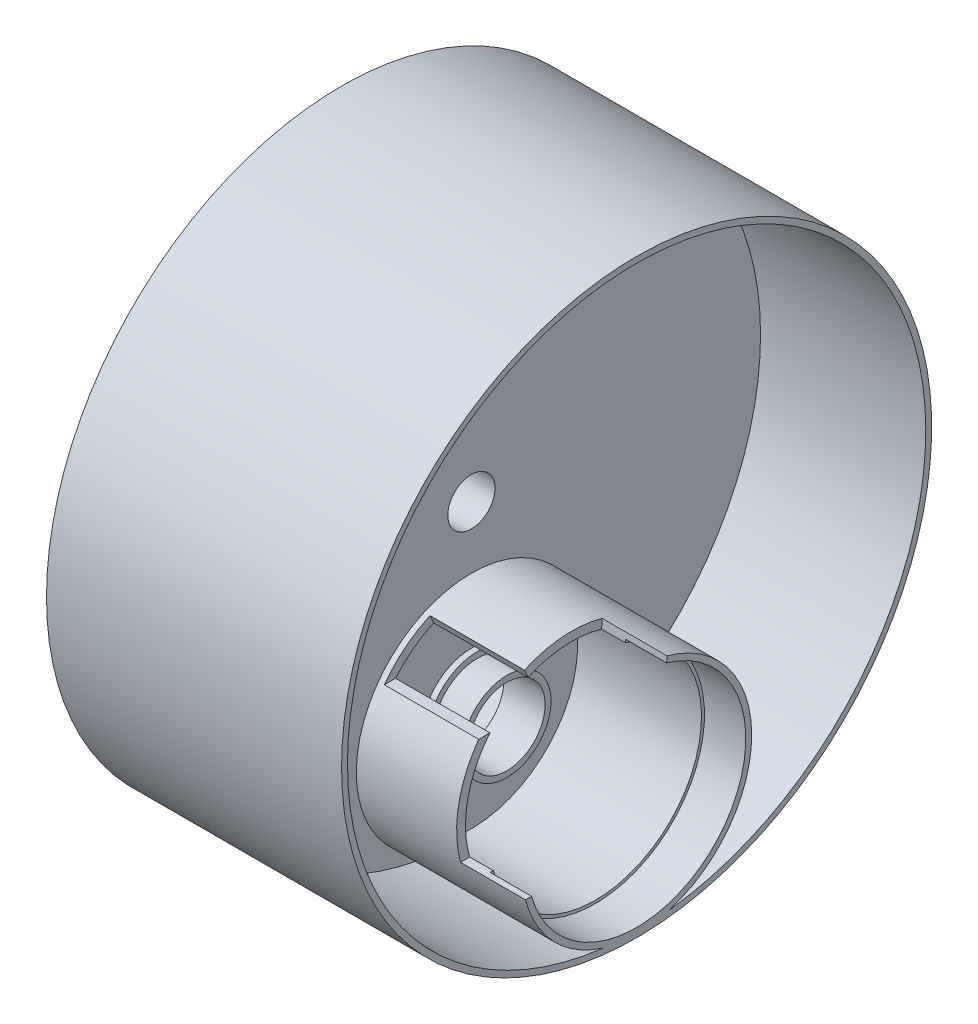
SolidWorks part; units mm, degrees
material "1060 Сплав"
ref_plane "Спереди" through (0, 0, 0) normal (0, 0, 1) x (1, 0, 0)
ref_plane "Сверху" through (0, 0, 0) normal (0, 1, 0) x (1, 0, 0)
ref_plane "Справа" through (0, 0, 0) normal (1, 0, 0) x (0, 0, -1)
sketch "Эскиз1" plane through (0, 0, 0) normal (0, 0, 1) x (1, 0, 0)
  line L0 (0, 0) -> (26039.5549, 0) construction
  line L1 (-27, 7.5) -> (-27, 8.5)
  line L2 (0, 19.5) -> (-29, 19.5)
  line L3 (-29, 19.5) -> (-29, 6.5)
  line L4 (-29, 6.5) -> (-22, 6.5)
  line L5 (-22, 6.5) -> (-22, 7.5)
  line L6 (-22, 7.5) -> (-27, 7.5)
  line L7 (-28, 8.5) -> (-28, 18)
  line L8 (-28, 18) -> (-7, 18)
  line L9 (-7, 18) -> (-7, 18.5)
  line L10 (-7, 18.5) -> (0, 18.5)
  line L11 (0, 18.5) -> (0, 19.5)
  line L12 (-27, 8.5) -> (-28, 8.5)
  dimension "D1" = 18.5
  dimension "D2" = 1
  dimension "D3" = 18
  dimension "D4" = 7
  dimension "D5" = 21
  dimension "D6" = 1
  dimension "D7" = 1
  dimension "D8" = 1
  dimension "D9" = 7.5
  dimension "D10" = 1
  dimension "D11" = 13
  dimension "D12" = 0.5
  dimension "D13" = 5
revolve "Повернуть1" add sketch "Эскиз1" angle 360 about L0
sketch "Эскиз2" plane through (0, 0, 0) normal (1, 0, 0) x (0, 0, -1)
  line L0 (0, 0) -> (0, 50000) construction
  line L1 (5.1563, 18.8059) -> (5, 16.2481)
  line L2 (5, 0) -> (5, 50000) construction
  line L3 (0, 0) -> (0, -5) construction
  line L4 (0, -5) -> (-50000, -5) construction
  line L5 (-18.8481, -5) -> (-16.2481, -5)
  line L6 (-5, 0) -> (-5, 50000) construction
  arc A0 (5, 16.2481) -> (-16.2481, -5) centre (0, 0) ccw
  arc A1 (-18.8481, -5) -> (5.1563, 18.8059) centre (0, 0) cw
  circle A2 centre (0, 0) radius 19.5 construction
  dimension "D3" = 17
  dimension "D4" = 19.5
  dimension "D1" = 5
  dimension "D2" = 5
  dimension "D5" = 2.5626
  dimension "D6" = 0
extrude "Вырез-Вытянуть1" cut sketch "Эскиз2" against normal blind 11 contours A0 L5 A1 L1
sketch "Эскиз3" plane through (0, 0, 0) normal (1, 0, 0) x (0, 0, -1)
  line L3 (-40, 11.5) -> (-12.52, 11.5)
  line L4 (0, 0) -> (-20535.6471, 45588.2353) construction
  line L5 (-6.9821, 15.5) -> (-13.2408, 29.394)
  line L6 (-13.2408, 29.394) -> (-40, 11.5)
  line L7 (0, 15.5) -> (-50000, 15.5) construction
  circle A0 centre (0, 0) radius 15.5 construction
  circle A1 centre (0, 0) radius 11.5 construction
  arc A2 (-6.9821, 15.5) -> (-12.52, 11.5) centre (0, 0) ccw
  dimension "D1" = 31
  dimension "D2" = 23
  dimension "D4" = 34
  dimension "D3" = 15.2386
  dimension "D5" = 32.1908
extrude "Вырез-Вытянуть2" cut sketch "Эскиз3" against normal blind 27
sketch "Эскиз4" plane through (-29, 0, 0) normal (-1, 0, 0) x (0, 0, 1)
  circle A1 centre (0, 30) radius 50
  circle A2 centre (0, 30) radius 4
  circle A3 centre (0, 0) radius 6.5 construction
  circle A4 centre (0, 0) radius 6.5
  dimension "D2" = 100
  dimension "D3" = 8
  dimension "D5" = 13
  dimension "D1" = 30
  dimension "D4" = 30
extrude "Бобышка-Вытянуть1" add sketch "Эскиз4" against normal blind 1
sketch "Эскиз5" plane through (-29, 0, 0) normal (-1, 0, 0) x (0, 0, 1)
  circle A0 centre (0, 30) radius 50
  circle A1 centre (0, 30) radius 49
  dimension "D1" = 100
  dimension "D2" = 98
extrude "Бобышка-Вытянуть2" add sketch "Эскиз5" against normal blind 29 and the other way blind 21
sketch "Эскиз6" plane through (-29, 0, 0) normal (-1, 0, 0) x (0, 0, 1)
  circle A0 centre (0, 30) radius 4
  circle A1 centre (0, 30) radius 5
  dimension "D1" = 10
  dimension "D2" = 8
extrude "Бобышка-Вытянуть3" add sketch "Эскиз6" along normal blind 20
